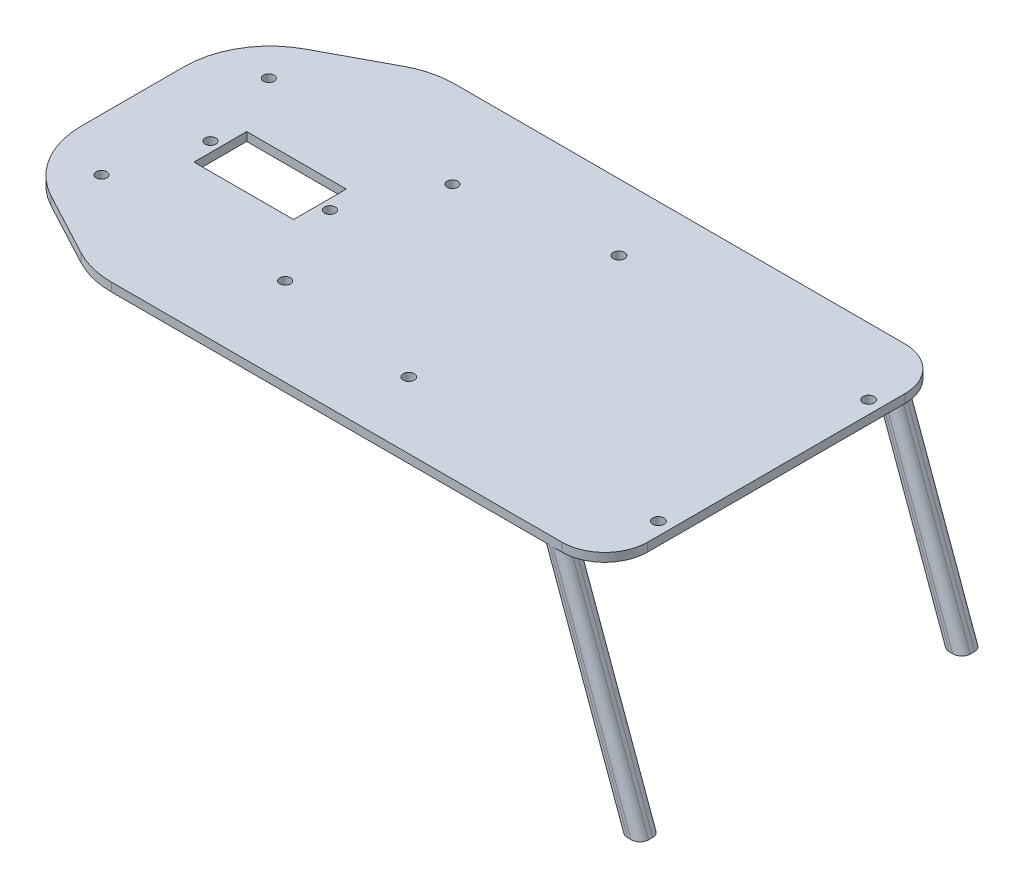
SolidWorks part; units mm, degrees
ref_plane "前视基准面" through (0, 0, 0) normal (0, 0, 1) x (1, 0, 0)
ref_plane "上视基准面" through (0, 0, 0) normal (0, 1, 0) x (1, 0, 0)
ref_plane "右视基准面" through (0, 0, 0) normal (1, 0, 0) x (0, 0, -1)
other "Configuration Table"
sketch "草图1" plane through (0, 0, 0) normal (0, 1, 0) x (1, 0, 0)
  line L0 (-41.4, 52.9432) -> (-41.4, -59.5525) construction
  line L1 (-75, -40) -> (75, -40)
  line L2 (-75, -40) -> (-75, 40)
  line L3 (-75, 40) -> (75, 40)
  line L4 (75, -40) -> (75, 40)
  line L5 (-75, -40) -> (75, 40) construction
  line L6 (-75, 40) -> (75, -40) construction
  line L7 (-75, 0) -> (32.4957, 0) construction
  circle A0 centre (-62.8, 19.5) radius 1.25
  circle A1 centre (-20, 19.5) radius 1.25
  circle A2 centre (-20, -19.5) radius 1.25
  circle A3 centre (-62.8, -19.5) radius 1.25
  point P0 (0, 0)
  dimension "D3" = 42.8
  dimension "D5" = 2.5
  dimension "D1" = 80
  dimension "D2" = 150
  dimension "D4" = 39
  dimension "D6" = 42.8
  dimension "D7" = 95
extrude "凸台-拉伸1" add sketch "草图1" along normal blind 2
sketch "草图2" plane through (0, 2, 0) normal (0, 1, 0) x (1, 0, 0)
  line L0 (-75, 0) -> (82.1354, 0) construction
  line L2 (42.9, 0) -> (42.9, 53.5496) construction
  line L3 (75, -40) -> (75, 40) construction
  circle A0 centre (13.8, 24.5) radius 1.3
  circle A1 centre (72, 24.5) radius 1.3
  circle A2 centre (13.8, -24.5) radius 1.3
  circle A3 centre (72, -24.5) radius 1.3
  dimension "D2" = 2.6
  dimension "D1" = 58.2
  dimension "D3" = 49
  dimension "D4" = 58.2
  dimension "D5" = 3
extrude "切除-拉伸1" cut sketch "草图2" against normal blind 2
sketch "草图3" plane through (0, 2, 0) normal (0, 1, 0) x (1, 0, 0)
  line L0 (0, 0) -> (90.8282, 0) construction
  line L1 (-75, 40) -> (-45, 40)
  line L2 (75, 40) -> (-75, 40) construction
  line L3 (-45, 40) -> (-75, 24)
  line L4 (-75, 40) -> (-75, -40) construction
  line L5 (-75, 24) -> (-75, 40)
  line L6 (-45, -40) -> (-75, -24)
  line L7 (-75, -40) -> (-45, -40)
  line L8 (-75, -24) -> (-75, -40)
  dimension "D1" = 30
  dimension "D2" = 16
extrude "切除-拉伸2" cut sketch "草图3" against normal blind 2
fillet "圆角1" radius 20 4 edges at (-45, 1, -40) (-75, 1, -24) (-45, 1, 40) (-75, 1, 24)
fillet "圆角2" radius 10 2 edges at (75, 1, -40) (75, 1, 40)
sketch "草图4" plane through (0, 2, 0) normal (0, 1, 0) x (1, 0, 0)
  line L0 (-75, 0) -> (35.4397, 0) construction
  line L2 (-75, 12) -> (-75, -12) construction
  line L3 (-54.6, -6.15) -> (-31.4, -6.15)
  line L4 (-54.6, -6.15) -> (-54.6, 6.15)
  line L5 (-54.6, 6.15) -> (-31.4, 6.15)
  line L6 (-31.4, -6.15) -> (-31.4, 6.15)
  line L7 (-54.6, -6.15) -> (-31.4, 6.15) construction
  line L8 (-54.6, 6.15) -> (-31.4, -6.15) construction
  line L9 (-43, 0) -> (-43, -46.9743) construction
  circle A0 centre (-29.075, 0) radius 1.25
  circle A1 centre (-56.925, 0) radius 1.25
  point P1 (-43, 0)
  dimension "D5" = 2.5
  dimension "D1" = 23.2
  dimension "D2" = 12.3
  dimension "D3" = 32
  dimension "D4" = 46.9743
  dimension "D6" = 27.85
extrude "切除-拉伸3" cut sketch "草图4" against normal up to next
sketch "草图5" plane through (0, 0, 40) normal (0, 0, 1) x (1, 0, 0)
  line L0 (65, 0) -> (83.1985, -50)
  line L1 (83.1985, -50) -> (78.1985, -50)
  line L2 (78.1985, -50) -> (60, 0)
  line L3 (60, 0) -> (65, 0)
  line L4 (-40, 0) -> (65, 0) construction
  dimension "D1" = 5
  dimension "D2" = 110
  dimension "D3" = 50
extrude "凸台-拉伸2" add sketch "草图5" against normal blind 5
mirror "镜向1" about plane through (0, 0, 0) normal (0, 0, 1) of "凸台-拉伸2"
fillet "圆角5" radius 2 8 edges at (69.0993, -25, 40) (74.0993, -25, 40) (69.0993, -25, 35) (74.0993, -25, 35) (74.0993, -25, -40) (74.0993, -25, -35) (69.0993, -25, -35) (69.0993, -25, -40)
